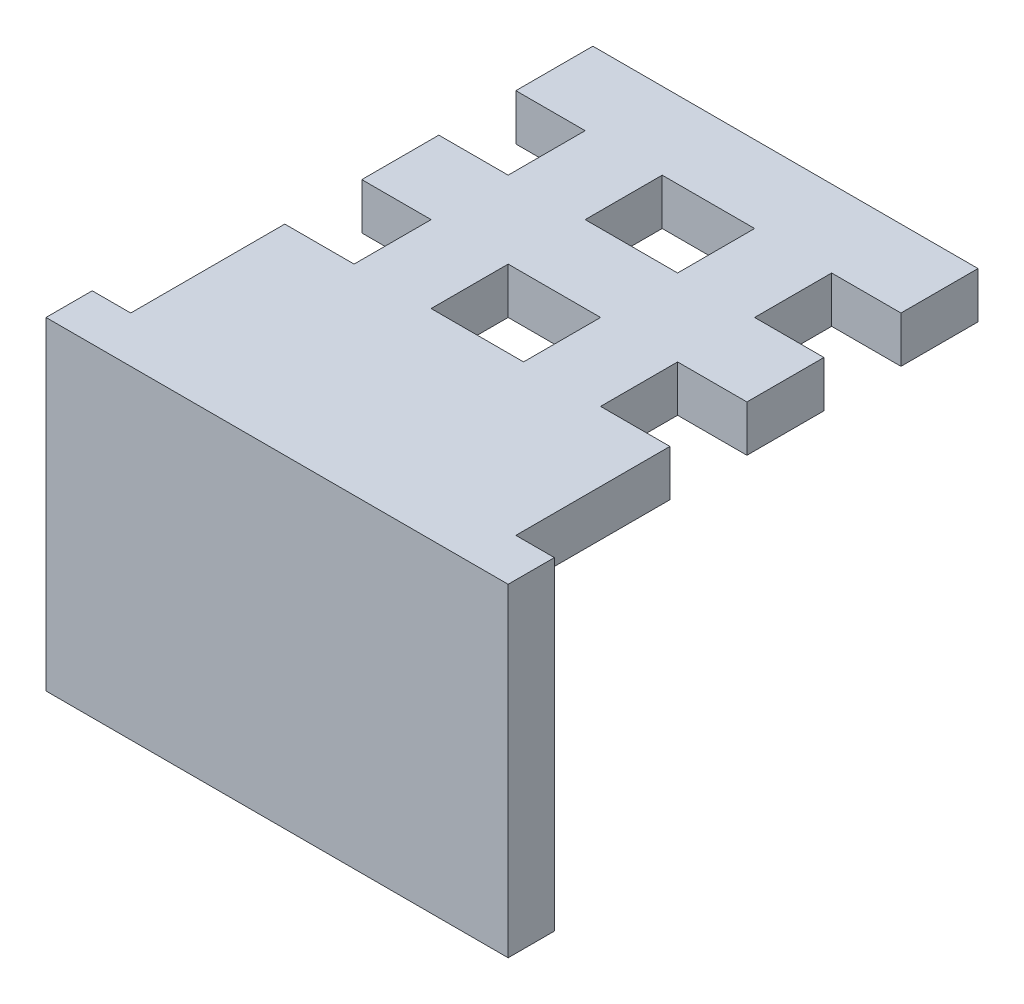
SolidWorks part; units mm, degrees
ref_plane "Front Plane" through (0, 0, 0) normal (0, 0, 1) x (1, 0, 0)
ref_plane "Top Plane" through (0, 0, 0) normal (0, 1, 0) x (1, 0, 0)
ref_plane "Right Plane" through (0, 0, 0) normal (1, 0, 0) x (0, 0, -1)
sketch "Sketch1" plane through (0, 0, 0) normal (0, 0, 1) x (1, 0, 0)
  line L1 (-150, 190) -> (150, 190)
  line L2 (-150, 190) -> (-150, -190)
  line L3 (-150, -190) -> (150, -190)
  line L4 (150, 190) -> (150, -190)
  line L5 (-150, 190) -> (150, -190) construction
  line L6 (-150, -190) -> (150, 190) construction
  point P0 (0, 0)
  dimension "D1" = 300
  dimension "D2" = 380
extrude "Boss-Extrude1" add sketch "Sketch1" along normal blind 30
sketch "Sketch2" plane through (0, 190, 0) normal (0, 1, 0) x (1, 0, 0)
  line L1 (-100, 300) -> (100, 300)
  line L2 (-100, 300) -> (-100, 50)
  line L3 (-100, 50) -> (100, 50)
  line L4 (100, 300) -> (100, 50)
  line L5 (-100, 300) -> (100, 50) construction
  line L6 (-100, 50) -> (100, 300) construction
  line L7 (0, 175) -> (0, 176.9125) construction
  line L8 (-60, 300) -> (-30, 300)
  line L9 (-60, 300) -> (-60, 50)
  line L10 (-60, 50) -> (-30, 50)
  line L11 (-30, 300) -> (-30, 50)
  line L12 (60, 300) -> (60, 50)
  line L13 (30, 300) -> (30, 50)
  line L14 (30, 300) -> (60, 300)
  line L15 (30, 50) -> (60, 50)
  line L17 (150, 0) -> (-150, 0) construction
  circle A0 centre (0, 175) radius 75
  circle A1 centre (0, 75) radius 10
  circle A2 centre (-80, 275) radius 10
  circle A3 centre (80, 275) radius 10
  point P0 (0, 175)
  dimension "D3" = 150
  dimension "D5" = 20
  dimension "D1" = 250
  dimension "D2" = 200
  dimension "D4" = 100
  dimension "D6" = 25
  dimension "D7" = 60
  dimension "D8" = 30
  dimension "D9" = 50
sketch "Sketch3" plane through (0, 0, 0) normal (0, 0, -1) x (-1, 0, 0)
  line L0 (-150, 190) -> (150, 190) construction
  line L1 (-125, 190) -> (125, 190)
  line L2 (-125, 190) -> (-125, 160)
  line L3 (-125, 160) -> (125, 160)
  line L4 (125, 190) -> (125, 160)
  point P6 (0, 160)
  dimension "D1" = 30
  dimension "D2" = 250
extrude "Boss-Extrude2" add sketch "Sketch3" along normal blind 100
extrude "Boss-Extrude3" add sketch "Sketch3<2>" along normal blind 50 from offset 150 separate body
sketch "Sketch3<2>" plane through (0, 0, 0) normal (0, 0, -1) x (-1, 0, 0) same geometry as "Sketch3"
extrude "Boss-Extrude4" add sketch "Sketch3<3>" along normal blind 50 from offset 250 separate body
sketch "Sketch3<3>" plane through (0, 0, 0) normal (0, 0, -1) x (-1, 0, 0) same geometry as "Sketch3"
sketch "Sketch4" plane through (0, 0, -150) normal (0, 0, 1) x (1, 0, 0)
  line L0 (-100, 190) -> (100, 190) construction
  line L1 (-80, 190) -> (-30, 190)
  line L2 (-80, 190) -> (-80, 160)
  line L3 (-80, 160) -> (-30, 160)
  line L4 (-30, 190) -> (-30, 160)
  line L5 (-100, 190) -> (100, 190) construction
  line L6 (30, 190) -> (80, 190)
  line L7 (30, 190) -> (30, 160)
  line L8 (30, 160) -> (80, 160)
  line L9 (80, 190) -> (80, 160)
  line L10 (0, 0) -> (0, 60.3573) construction
  dimension "D1" = 30
  dimension "D2" = 50
  dimension "D3" = 60
extrude "Boss-Extrude5" add sketch "Sketch4" along normal up to next
extrude "Boss-Extrude6" add sketch "Sketch4<2>" against normal blind 50 from offset 50 offset against normal yes
sketch "Sketch4<2>" plane through (0, 0, -150) normal (0, 0, 1) x (1, 0, 0) same geometry as "Sketch4"
sketch "Sketch5" plane through (0, 160, 0) normal (0, -1, 0) x (1, 0, 0)
  circle A0 centre (-80, -275) radius 10
  circle A1 centre (80, -275) radius 10
  circle A2 centre (0, -75) radius 10
  circle A3 centre (-80, -275) radius 10 construction
extrude "Cut-Extrude1" cut sketch "Sketch5" against normal blind 10
sketch "Sketch6" plane through (0, 0, 0) normal (0, 0, -1) x (-1, 0, 0)
  line L0 (0, 0) -> (0, 165.1492) construction
  line L5 (-150, 190) -> (-125, 190) construction
  circle A0 centre (-45, 40) radius 5
  circle A2 centre (45, 40) radius 5
  dimension "D1" = 10
  dimension "D2" = 150
  dimension "D3" = 45
extrude "Cut-Extrude2" cut sketch "Sketch6" against normal blind 10
sketch "Sketch7" plane through (0, 0, 0) normal (0, 0, -1) x (-1, 0, 0)
  line L0 (150, 190) -> (150, -190) construction
  line L1 (-150, -190) -> (150, -190)
  line L2 (-150, -190) -> (-150, -20)
  line L3 (-150, -20) -> (150, -20)
  line L4 (150, -190) -> (150, -20)
  dimension "D1" = 170
extrude "Cut-Extrude3" cut sketch "Sketch7" against normal blind 30
